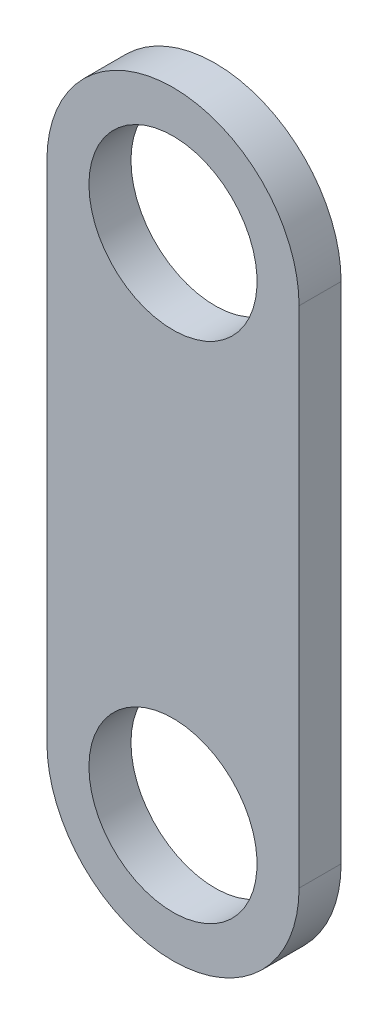
SolidWorks part; units mm, degrees
ref_plane "Front Plane" through (0, 0, 0) normal (0, 0, 1) x (1, 0, 0)
ref_plane "Top Plane" through (0, 0, 0) normal (0, 1, 0) x (1, 0, 0)
ref_plane "Right Plane" through (0, 0, 0) normal (1, 0, 0) x (0, 0, -1)
sketch "Sketch1" plane through (0, 0, 0) normal (0, 0, 1) x (1, 0, 0)
  line L0 (-29.7399, 28.1638) -> (-29.7399, -48.0362)
  line L1 (8.3601, 28.1638) -> (8.3601, -48.0362)
  arc A0 (-29.7399, 28.1638) -> (8.3601, 28.1638) centre (-10.6899, 28.1638) cw
  arc A1 (-29.7399, -48.0362) -> (8.3601, -48.0362) centre (-10.6899, -48.0362) ccw
  circle A2 centre (-10.6899, 28.1638) radius 12.7
  circle A3 centre (-10.6899, -48.0362) radius 12.7
  dimension "D3" = 25.4
  dimension "D4" = 25.4
  dimension "D1" = 76.2
  dimension "D2" = 38.1
extrude "Boss-Extrude2" add sketch "Sketch1" along normal blind 6.35 contours A0 L1 A1 L0
sketch "Sketch2" plane through (0, 0, 0) normal (0, 0, -1) x (-1, 0, 0)
  circle A0 centre (10.6899, 28.1638) radius 12.7
  circle A2 centre (10.6899, -48.0362) radius 12.7
  dimension "D1" = 25.4
  dimension "D2" = 25.4
extrude "Cut-Extrude1" cut sketch "Sketch2" against normal through all
equation "\"Link length\" = 3"
equation "\"Anet\"= 0.125"
equation "\"width\"= 1.50"
equation "\"extrude\"= 1 / 4"
equation "\"actual width\" = ( \"Anet\" / \"extrude\" ) + 1.00"
equation "\"D1@Sketch1\"=\"Link length\""
equation "\"D2@Sketch1\"=\"actual width\""
equation "\"diameter\"= ( \"Anet\" / \"extrude\" - \"actual width\" ) / - 1.00"
equation "\"D4@Sketch1\"=\"diameter\""
equation "\"D3@Sketch1\"=\"diameter\""
equation "\"D1@Boss-Extrude2\"=\"extrude\""
equation "\"D1@Sketch2\"=\"diameter\""
equation "\"D2@Sketch2\"=\"diameter\""
equation "\"D1@Sketch3\" = \""
